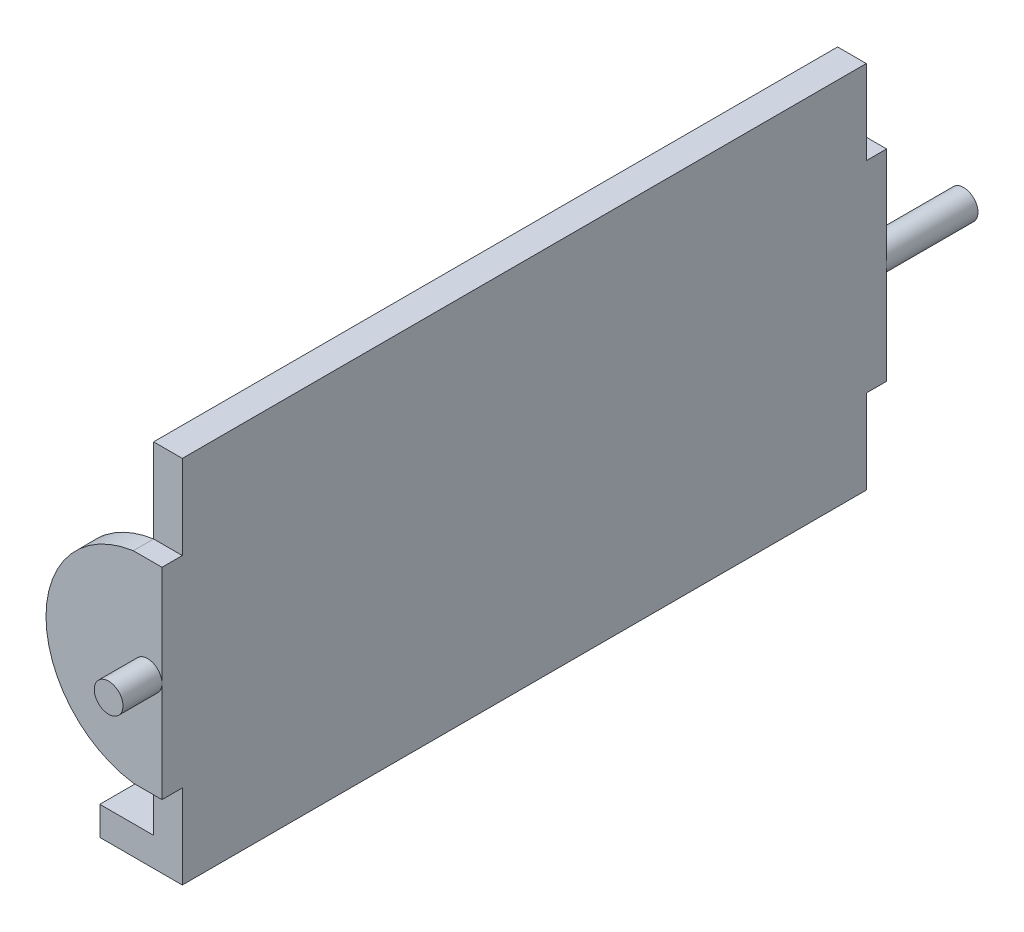
SolidWorks part; units mm, degrees
ref_plane "Front Plane" through (0, 0, 0) normal (0, 0, 1) x (1, 0, 0)
ref_plane "Top Plane" through (0, 0, 0) normal (0, 1, 0) x (1, 0, 0)
ref_plane "Right Plane" through (0, 0, 0) normal (1, 0, 0) x (0, 0, -1)
sketch "Sketch1" plane through (0, 0, 0) normal (0, 0, 1) x (1, 0, 0)
  line L0 (-6.096, 78.486) -> (-6.096, 6.096)
  line L1 (-6.096, 6.096) -> (-17.526, 6.096)
  line L4 (-17.526, 6.096) -> (-17.526, 0)
  line L5 (-17.526, 0) -> (0, 0)
  line L6 (0, 0) -> (0, 78.486)
  line L8 (-6.096, 78.486) -> (0, 78.486)
  dimension "D1" = 6.096
  dimension "D2" = 6.096
  dimension "D3" = 11.43
  dimension "D5" = 72.39
extrude "Boss-Extrude1" add sketch "Sketch1" along normal mid plane 145.288
ref_plane "Plane2" through (0, 39.243, 0) normal (0, 1, 0) x (1, 0, 0)
sketch "Sketch5" plane through (0, 0, 0) normal (0, 0, 1) x (1, 0, 0)
  line L0 (-6.096, 78.486) -> (-6.096, 6.096) construction
  line L3 (9.6393, 39.243) -> (-9.6393, 39.243) construction
  circle A0 centre (-3.048, 39.243) radius 3.048
  dimension "D1" = 6.096
extrude "Boss-Extrude3" add sketch "Sketch5" along normal up to surface (85.2488 mm away) and the other way up to surface (96.3739 mm away)
sketch "Sketch7" plane through (0, 0, -72.644) normal (0, 0, -1) x (-1, 0, 0)
  line L0 (6.096, 78.486) -> (6.096, 39.243) construction
  line L1 (6.096, 39.243) -> (6.096, 6.096) construction
  line L2 (6.096, 60.6168) -> (0, 60.6168)
  line L4 (6.096, 17.8692) -> (0, 17.8692)
  line L6 (0, 39.243) -> (0, 78.486) construction
  line L7 (0, 60.6168) -> (0, 17.8692)
  arc A0 (6.096, 60.6168) -> (6.096, 17.8692) centre (3.048, 39.243) cw
  dimension "D1" = 21.59
extrude "Boss-Extrude4" add sketch "Sketch7" along normal blind 4.318
sketch "Sketch8" plane through (0, 0, -72.644) normal (0, 0, 1) x (1, 0, 0)
  line L0 (-15.748, 56.7026) -> (-15.748, 21.7834)
  line L1 (-6.096, 60.6168) -> (-6.096, 17.8692) construction
  arc A0 (-6.096, 60.6168) -> (-6.096, 17.8692) centre (-3.048, 39.243) ccw construction
  arc A1 (-15.748, 56.7026) -> (-15.748, 21.7834) centre (-3.048, 39.243) ccw
  dimension "D1" = 9.652
extrude "Boss-Extrude5" add sketch "Sketch8" along normal blind 7.62
ref_plane "Plane3" through (-15.748, 56.7026, -65.024) normal (0, 1, 0) x (1, 0, 0)
sketch "Sketch10" plane through (-15.748, 0, 0) normal (1, 0, 0) x (0, 0, -1)
  line L0 (65.024, 21.7834) -> (72.644, 21.7834) construction
  line L2 (65.024, 56.7026) -> (72.644, 56.7026) construction
  line L3 (65.024, 56.7026) -> (65.024, 21.7834) construction
  line L4 (65.024, 49.0826) -> (65.024, 56.7026)
  line L5 (65.024, 56.7026) -> (72.644, 56.7026)
  line L6 (72.644, 21.7834) -> (65.024, 21.7834)
  line L7 (65.024, 21.7834) -> (65.024, 29.4034)
  arc A0 (72.644, 56.7026) -> (65.024, 49.0826) centre (72.644, 49.0826) ccw
  arc A1 (72.644, 21.7834) -> (65.024, 29.4034) centre (72.644, 29.4034) cw
extrude "Cut-Extrude1" cut sketch "Sketch10" against normal blind 7.62
mirror "Mirror1" about plane through (0, 0, 0) normal (0, 0, 1) of "Cut-Extrude1", "Boss-Extrude5", "Boss-Extrude4"
fillet "Fillet1" radius 7.62 2 edges at (-24.638, 39.243, -65.024) (-24.638, 39.243, 65.024)
fillet "Fillet2" radius 1.27 4 edges at (-15.748, 23.2189, 68.6292) (-15.748, 53.4258, 66.9536) (-15.748, 25.0602, -66.9536) (-15.748, 55.2671, -68.6292)
